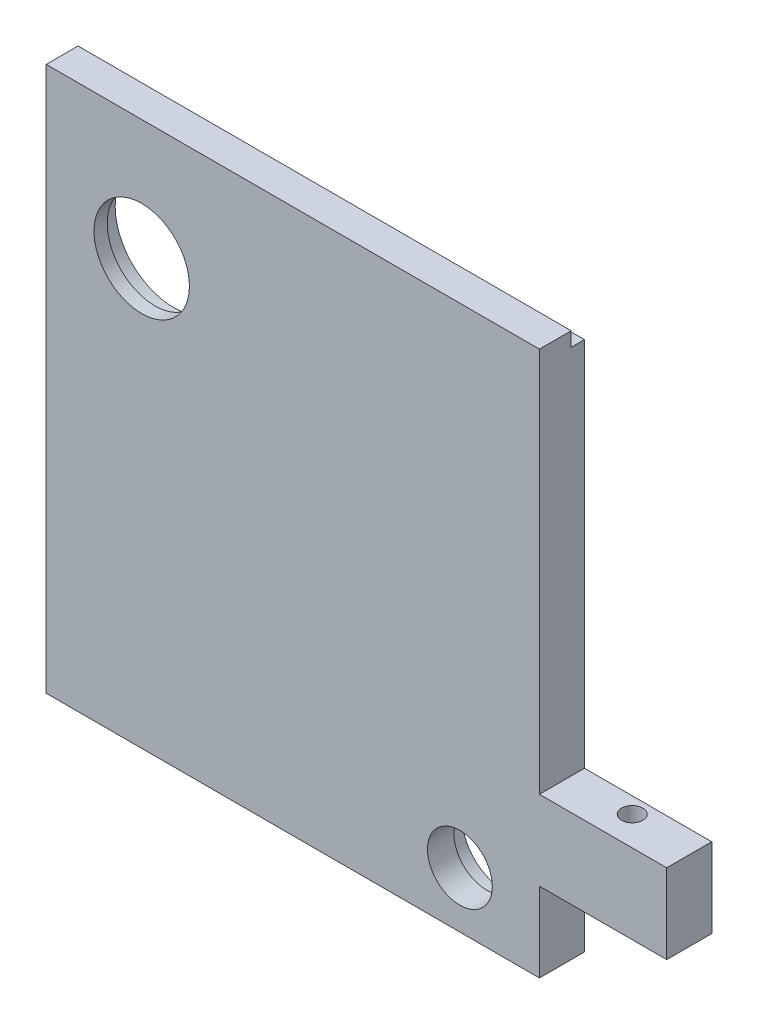
SolidWorks part; units mm, degrees
ref_plane "Front Plane" through (0, 0, 0) normal (0, 0, 1) x (1, 0, 0)
ref_plane "Top Plane" through (0, 0, 0) normal (0, 1, 0) x (1, 0, 0)
ref_plane "Right Plane" through (0, 0, 0) normal (1, 0, 0) x (0, 0, -1)
sketch "Sketch1" plane through (0, 0, 0) normal (0, 0, 1) x (1, 0, 0)
  line L1 (-76.1871, 67.6281) -> (16.8129, 67.6281)
  line L2 (-76.1871, 67.6281) -> (-76.1871, -35.0719)
  line L3 (-76.1871, -35.0719) -> (16.8129, -35.0719)
  line L4 (16.8129, 67.6281) -> (16.8129, -35.0719)
  dimension "D1" = 93
  dimension "D2" = 102.7
extrude "Boss-Extrude2" add sketch "Sketch1" along normal blind 6 contours L1 L4 L3 L2
sketch "Sketch3" plane through (0, 0, 0) normal (0, 0, -1) x (-1, 0, 0)
  line L0 (76.1871, -35.0719) -> (-16.8129, -35.0719) construction
  line L1 (-16.8129, 64.9281) -> (18.1871, 64.9281)
  line L2 (-16.8129, 64.9281) -> (-16.8129, -35.0719)
  line L3 (-16.8129, -35.0719) -> (18.1871, -35.0719)
  line L4 (18.1871, 64.9281) -> (18.1871, -35.0719)
  line L5 (-16.8129, 67.6281) -> (-16.8129, -35.0719) construction
  dimension "D1" = 0
  dimension "D2" = 0
  dimension "D3" = 35
  dimension "D4" = 100
extrude "Boss-Extrude3" add sketch "Sketch3" along normal blind 2.5
sketch "Sketch4" plane through (16.8129, 0, 0) normal (1, 0, 0) x (0, 0, -1)
  line L0 (-6, 67.6281) -> (-6, -35.0719) construction
  line L1 (-6, -5.0719) -> (2.5, -5.0719)
  line L2 (-6, -5.0719) -> (-6, -20.0719)
  line L3 (-6, -20.0719) -> (2.5, -20.0719)
  line L4 (2.5, -5.0719) -> (2.5, -20.0719)
  line L5 (2.5, 64.9281) -> (2.5, -35.0719) construction
  line L6 (-6, -35.0719) -> (2.5, -35.0719) construction
  dimension "D1" = 15
  dimension "D2" = 15
extrude "Boss-Extrude4" add sketch "Sketch4" along normal blind 24
sketch "Sketch5" plane through (0, -5.0719, 0) normal (0, 1, 0) x (1, 0, 0)
  line L0 (40.8129, -6) -> (16.8129, -6) construction
  line L2 (16.8129, 2.5) -> (16.8129, -6) construction
  circle A0 centre (28.8129, -0.5) radius 2
  dimension "D2" = 4
  dimension "D3" = 12
  dimension "D1" = 5.5
extrude "Cut-Extrude1" cut sketch "Sketch5" against normal blind 50
sketch "Sketch6" plane through (0, 0, -2.5) normal (0, 0, -1) x (-1, 0, 0)
  line L0 (-16.8129, -35.0719) -> (18.1871, -35.0719) construction
  line L1 (-16.8129, -20.0719) -> (-16.8129, -35.0719) construction
  circle A0 centre (-1.8129, -24.5719) radius 8.115
  dimension "D1" = 16.23
  dimension "D2" = 10.5
  dimension "D3" = 15
extrude "Cut-Extrude2" cut sketch "Sketch6" against normal blind 50
sketch "Sketch7" plane through (0, 0, 0) normal (0, 0, -1) x (-1, 0, 0)
  line L0 (76.1871, -35.0719) -> (18.1871, -35.0719) construction
  line L2 (-16.8129, 64.9281) -> (-16.8129, -5.0719) construction
  circle A0 centre (58.1871, 44.9281) radius 11
  dimension "D1" = 22
  dimension "D2" = 80
  dimension "D3" = 75
extrude "Cut-Extrude3" cut sketch "Sketch7" against normal blind 50
extrude "Extrude-Thin1" add sketch "Sketch7" along normal blind 2.5 from surface thin starting at face at (-47.1871, 44.9281, 6) thin type one direction reverse wall 2
extrude "Extrude-Thin2" add sketch "Sketch6<2>" along normal blind 5 from surface thin starting at face at (9.9279, -24.5719, 6) thin type one direction reverse wall 2
sketch "Sketch6<2>" plane through (0, 0, -2.5) normal (0, 0, -1) x (-1, 0, 0) same geometry as "Sketch6"
